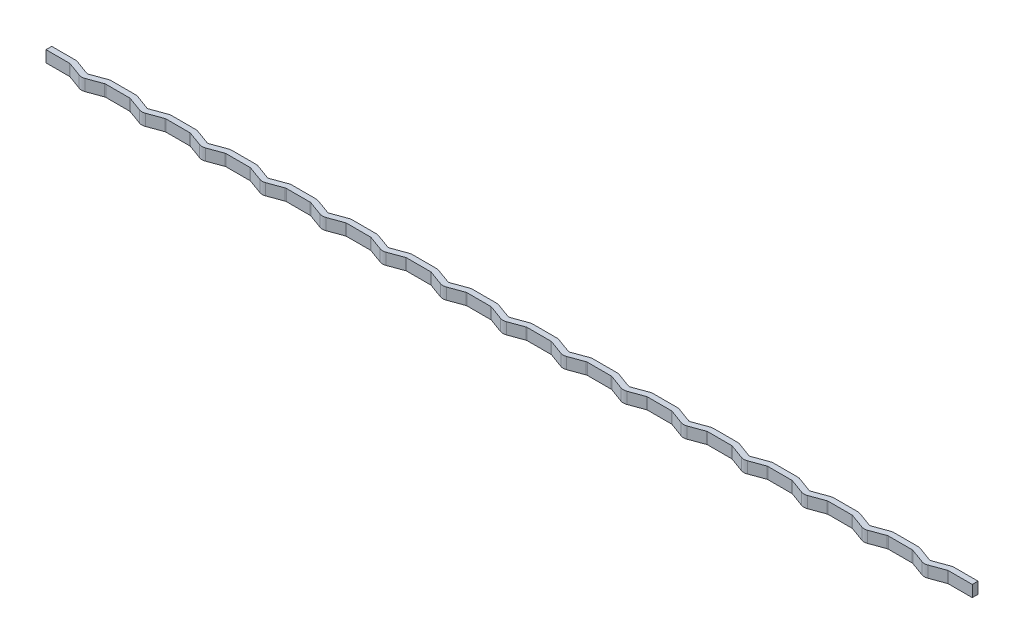
SolidWorks part; units mm, degrees
material "Rubber"
ref_plane "Front Plane" through (0, 0, 0) normal (0, 0, 1) x (1, 0, 0)
ref_plane "Top Plane" through (0, 0, 0) normal (0, 1, 0) x (1, 0, 0)
ref_plane "Right Plane" through (0, 0, 0) normal (1, 0, 0) x (0, 0, -1)
sketch "Sketch1" plane through (0, 0, 0) normal (0, 1, 0) x (1, 0, 0)
  line L0 (0, 0) -> (4.0737, 0)
  line L1 (4.25, 0) -> (10.25, 0) construction
  line L2 (7.25, 0.5445) -> (7.25, -3.0811) construction
  line L3 (10.4263, 0) -> (10.75, 0)
  line L4 (4.4157, -0.0603) -> (6.908, -0.9674)
  line L5 (7.592, -0.9674) -> (10.0843, -0.0603)
  line L6 (0, -0.5) -> (4.0737, -0.5)
  line L7 (4.2447, -0.5302) -> (6.737, -1.4373)
  line L8 (7.763, -1.4373) -> (10.2553, -0.5302)
  line L9 (10.4263, -0.5) -> (10.75, -0.5)
  line L10 (0, 0.5) -> (4.0737, 0.5)
  line L11 (4.5867, 0.4095) -> (7.079, -0.4976)
  line L12 (7.421, -0.4976) -> (9.9133, 0.4095)
  line L13 (10.4263, 0.5) -> (10.75, 0.5)
  line L14 (0, 0.5) -> (0, -0.5)
  line L15 (10.75, 0.5) -> (10.75, -0.5)
  arc A0 (4.4157, -0.0603) -> (4.0737, 0) centre (4.0737, -1) ccw
  arc A1 (10.4263, 0) -> (10.0843, -0.0603) centre (10.4263, -1) ccw
  arc A2 (7.592, -0.9674) -> (6.908, -0.9674) centre (7.25, -0.0277) cw
  arc A3 (4.2447, -0.5302) -> (4.0737, -0.5) centre (4.0737, -1) ccw
  arc A4 (7.763, -1.4373) -> (6.737, -1.4373) centre (7.25, -0.0277) cw
  arc A5 (10.4263, -0.5) -> (10.2553, -0.5302) centre (10.4263, -1) ccw
  arc A6 (4.5867, 0.4095) -> (4.0737, 0.5) centre (4.0737, -1) ccw
  arc A7 (7.421, -0.4976) -> (7.079, -0.4976) centre (7.25, -0.0277) cw
  arc A8 (10.4263, 0.5) -> (9.9133, 0.4095) centre (10.4263, -1) ccw
  point P17 (7.25, -1.0919)
  dimension "D5" = 1
  dimension "D6" = 1
  dimension "D7" = 1
  dimension "D1" = 4.25
  dimension "D2" = 6
  dimension "D3" = 0.5
  dimension "D4" = 160
  dimension "Section Length" = 10.75
  dimension "D10" = 4.0737
  dimension "D8" = 0.5
  dimension "D9" = 0.5
extrude "Boss-Extrude1" add sketch "Sketch1" along normal blind 2 contours L10 A6 L11 A7 L12 A8 L13 L15 L9 A5 L8 A4 L7 A3 L6 L14
pattern_linear "LPattern1" count 15 spacing 10.5 along (1, 0, 0) of "Boss-Extrude1"
sketch "Sketch2" plane through (0, 0, 0) normal (-1, 0, 0) x (0, 0, 1)
  line L1 (-0.5, 2) -> (0.5, 2)
  line L2 (-0.5, 2) -> (-0.5, 0)
  line L3 (-0.5, 0) -> (0.5, 0)
  line L4 (0.5, 2) -> (0.5, 0)
extrude "Boss-Extrude2" add sketch "Sketch2" against normal blind 4.0737 from offset 157.5 offset against normal yes
equation "\"OuterThickness\"= 3mm"
equation "\"MasterFillet\"= 3mm"
equation "\"PartSeperation\"= 6mm"
equation "\"D1@Sketch1\" = \"DiscThickness\" + \"LigamentExtension\" / 4"
equation "\"D2@Sketch1\"=\"PartSeperation\""
equation "\"D3@Sketch1\"=\"LigamentExtension\"/2"
equation "\"D4@Sketch1\" = 180 - \"LigamentAngle\""
equation "\"D7@Sketch1\"=\"MasterFillet\"/3"
equation "\"D6@Sketch1\"=\"MasterFillet\"/3"
equation "\"D5@Sketch1\"=\"MasterFillet\"/3"
equation "\"D9@Sketch1\" = \"LigamentDepth\" / 2"
equation "\"D8@Sketch1\" = \"LigamentDepth\" / 2"
equation "\"D1@Boss-Extrude1\" = \"LigamentThickness\""
equation "\"D3@LPattern1\"= \"DiscThickness\" + \"LigamentExtension\" / 2 + \"PartSeperation\""
equation "\"Tolerance\"= 0.15mm"
equation "\"HeightPart\"= 100mm"
equation "\"Holes\"= 1.5mm"
equation "\"SpineHolderThickness\"= 3mm"
equation "\"SpineHolderDepth\" = 3mm"
equation "\"LigamentExtension\"= 1mm"
equation "\"MotorLength\" = 40.5mm"
equation "\"MotorWidth\" = 20.3mm"
equation "\"AttachmentHeight\"= 3mm"
equation "\"SpoolDiameter\"= 60mm"
equation "\"SpoolHeight\"= 2mm"
equation "\"SpoolRidgeHeight\"= 1mm"
equation "\"SpoolRidgeDepth\"= 2mm"
equation "\"SpoolSeperation\"= 2mm"
equation "\"ServoHolderWidthOffset\"= 20mm"
equation "\"MotorTransmitterToScrew\"= 21.7mm"
equation "\"SpoolToSpine\"= 15mm"
equation "\"SpoolCenterToMotor\" = 31.5mm"
equation "\"HubOffset\"= 18mm"
equation "\"ServoFastenerHolders\"=2mm"
equation "\"ArduinoLength\" = 53.4mm"
equation "\"ArduinoWidth\" = 50mm"
equation "\"ArdYOffset\" = 29.5mm"
equation "\"ArdXOffset\" = 20.5mm"
equation "\"ArdXOffsetSmall\" = 25mm"
equation "\"MiddleServoOffset\"= 12mm"
equation "\"LargeServoOffset\"= 3mm"
equation "\"SmallServoOffset\"= 0mm"
equation "\"ToolHoleDiameter\"= 12mm"
equation "\"DiscThickness\"= 4mm"
equation "\"LigamentThickness\"= 2mm"
equation "\"LigamentAngle\"= 20deg"
equation "\"SpineDiameter\"= 15mm"
equation "\"LigamentDepth\"= 1mm"
equation "\"NoOfSegments\"= 3"
equation "\"DisksInSegments\"= 5"
equation "\"D1@LPattern1\"=\"NoOfSegments\"*\"DisksInSegments\""
equation "\"D19@Boss-Extrude2\"=(\"DiscThickness\" + \"LigamentExtension\" / 2 + \"PartSeperation\")*\"NoOfSegments\"*\"DisksInSegments\""
equation "\"D1@Boss-Extrude2\"=\"D10@Sketch1\""
equation "\"TendonExtension\" = 1mm"
